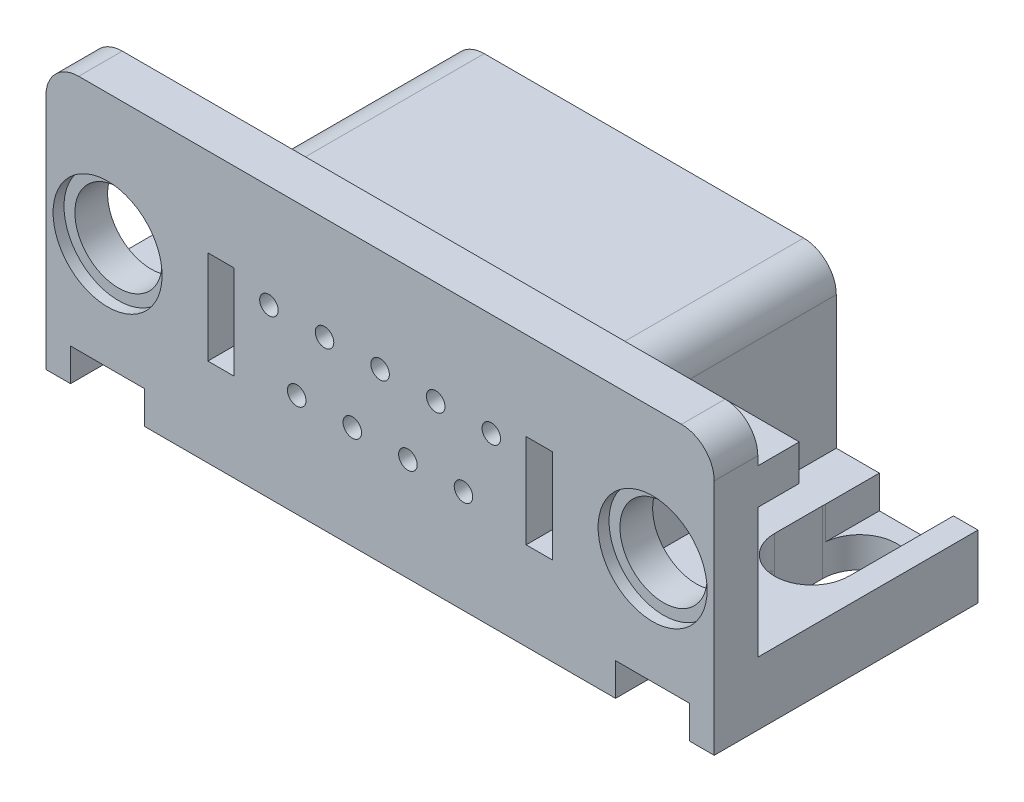
SolidWorks part; units mm, degrees
ref_plane "Front Plane" through (0, 0, 0) normal (0, 0, 1) x (1, 0, 0)
ref_plane "Top Plane" through (0, 0, 0) normal (0, 1, 0) x (1, 0, 0)
ref_plane "Right Plane" through (0, 0, 0) normal (1, 0, 0) x (0, 0, -1)
sketch "Sketch1" plane through (0, 0, 0) normal (0, 1, 0) x (1, 0, 0)
  line L1 (15.325, 6.05) -> (-15.325, 6.05)
  line L2 (15.325, 6.05) -> (15.325, -6.05)
  line L3 (15.325, -6.05) -> (-15.325, -6.05)
  line L4 (-15.325, 6.05) -> (-15.325, -6.05)
  line L5 (15.325, 6.05) -> (-15.325, -6.05) construction
  line L6 (15.325, -6.05) -> (-15.325, 6.05) construction
  point P0 (0, 0)
  dimension "D1" = 30.65
  dimension "D2" = 12.1
extrude "Boss-Extrude1" add sketch "Sketch1" along normal blind 12.4
sketch "Sketch2" plane through (0, 0, 6.05) normal (0, 0, 1) x (1, 0, 0)
  line L0 (-15.325, 12.4) -> (15.325, 12.4) construction
  line L2 (0, 0) -> (0, 12.4) construction
  line L4 (-6.7, 8.35) -> (-7.9, 8.35)
  line L5 (-6.7, 8.35) -> (-6.7, 4.05)
  line L6 (-6.7, 4.05) -> (-7.9, 4.05)
  line L7 (-7.9, 8.35) -> (-7.9, 4.05)
  line L8 (-6.7, 8.35) -> (-7.9, 4.05) construction
  line L9 (-6.7, 4.05) -> (-7.9, 8.35) construction
  line L14 (-15.325, 0) -> (15.325, 0) construction
  line L15 (6.7, 4.05) -> (7.9, 8.35) construction
  line L16 (6.7, 8.35) -> (7.9, 4.05) construction
  line L17 (7.9, 8.35) -> (7.9, 4.05)
  line L18 (6.7, 4.05) -> (7.9, 4.05)
  line L19 (6.7, 8.35) -> (6.7, 4.05)
  line L20 (6.7, 8.35) -> (7.9, 8.35)
  circle A0 centre (-12.5, 6.4) radius 2
  circle A1 centre (12.5, 6.4) radius 2
  point P10 (-7.3, 6.2)
  point P21 (7.3, 6.2)
  dimension "D1" = 4
  dimension "D2" = 14.5
  dimension "D3" = 6
  dimension "D4" = 4.3
  dimension "D5" = 6.7
  dimension "D6" = 1.2
  dimension "D7" = 4.05
extrude "Cut-Extrude1" cut sketch "Sketch2" against normal blind 10
sketch "Sketch3" plane through (0, 0, 6.05) normal (0, 0, 1) x (1, 0, 0)
  line L5 (-15.325, 12.4) -> (15.325, 12.4) construction
  line L6 (-15.325, 0) -> (15.325, 0) construction
  circle A0 centre (-5.1, 7.675) radius 0.425
  circle A2 centre (-2.55, 7.675) radius 0.425
  circle A3 centre (0, 7.675) radius 0.425
  circle A4 centre (2.55, 7.675) radius 0.425
  circle A5 centre (5.1, 7.675) radius 0.425
  circle A6 centre (-3.825, 4.725) radius 0.425
  circle A7 centre (-1.275, 4.725) radius 0.425
  circle A8 centre (1.275, 4.725) radius 0.425
  circle A9 centre (3.825, 4.725) radius 0.425
  dimension "D1" = 0.85
  dimension "D3" = 4.3
  dimension "D4" = 5
  dimension "D5" = 0.85
  dimension "D2" = 2.55
  dimension "D7" = 4.3
  dimension "D9" = 2.55
  dimension "D6" = 1.275
  dimension "D8" = 4
extrude "Cut-Extrude2" cut sketch "Sketch3" against normal blind 12.4
sketch "Sketch4" plane through (0, 0, -6.05) normal (0, 0, -1) x (-1, 0, 0)
  line L0 (15.325, 12.4) -> (15.325, 0) construction
  line L1 (-15.325, 12.4) -> (15.325, 12.4)
  line L2 (-15.325, 12.4) -> (-15.325, 10.5)
  line L3 (-15.325, 10.5) -> (15.325, 10.5)
  line L4 (15.325, 12.4) -> (15.325, 10.5)
  line L5 (-15.325, 0) -> (15.325, 0) construction
  line L6 (-8.8, 0) -> (8.8, 0)
  line L7 (-8.8, 0) -> (-8.8, 0.8)
  line L8 (-8.8, 0.8) -> (8.8, 0.8)
  line L9 (8.8, 0) -> (8.8, 0.8)
  line L10 (0, 0) -> (0, 10.5) construction
  line L11 (15.325, 8.85) -> (8.825, 8.85)
  line L12 (15.325, 8.85) -> (15.325, 2.9)
  line L13 (15.325, 2.9) -> (8.825, 2.9)
  line L14 (8.825, 8.85) -> (8.825, 2.9)
  line L15 (-15.325, 2.9) -> (-8.825, 2.9)
  line L16 (-8.825, 8.85) -> (-8.825, 2.9)
  line L17 (-15.325, 8.85) -> (-8.825, 8.85)
  line L18 (-15.325, 8.85) -> (-15.325, 2.9)
  point P13 (0, 0.8)
  dimension "D1" = 1.9
  dimension "D2" = 17.6
  dimension "D3" = 0.8
  dimension "D4" = 1.65
  dimension "D5" = 6.5
  dimension "D6" = 2.9
extrude "Cut-Extrude3" cut sketch "Sketch4" against normal blind 10.1
sketch "Sketch6" plane through (0, 10.5, 0) normal (0, 1, 0) x (1, 0, 0)
  line L0 (-15.325, -6.05) -> (15.325, -6.05) construction
  line L1 (15.325, 6.05) -> (8.825, 6.05)
  line L2 (15.325, 6.05) -> (15.325, -2.15)
  line L3 (15.325, -2.15) -> (8.825, -2.15)
  line L4 (8.825, 6.05) -> (8.825, -2.15)
  line L7 (0, 0) -> (0, -6.05) construction
  line L8 (-8.825, 6.05) -> (-8.825, -2.15)
  line L9 (-15.325, -2.15) -> (-8.825, -2.15)
  line L10 (-15.325, 6.05) -> (-15.325, -2.15)
  line L11 (-15.325, 6.05) -> (-8.825, 6.05)
  dimension "D1" = 3.9
  dimension "D2" = 6.5
extrude "Cut-Extrude4" cut sketch "Sketch6" against normal up to next
sketch "Sketch7" plane through (0, 0, -6.05) normal (0, 0, -1) x (-1, 0, 0)
  line L5 (-15.325, 9.5) -> (15.325, 9.5)
  line L6 (-7.825, 9.5) -> (7.825, 9.5)
  line L8 (-7.825, 2.9) -> (-7.825, 10.5)
  line L9 (-7.825, 2.9) -> (-7.825, 9.5)
  line L10 (-7.825, 2.9) -> (7.825, 2.9)
  line L11 (7.825, 10.5) -> (7.825, 2.9)
  line L12 (7.825, 9.5) -> (7.825, 2.9)
  dimension "D2" = 1
  dimension "D1" = 1
  dimension "D3" = 1
extrude "Cut-Extrude5" cut sketch "Sketch7" against normal blind 6.35
sketch "Sketch8" plane through (0, 2.9, 0) normal (0, 1, 0) x (1, 0, 0)
  line L0 (-12.495, 3.45) -> (-12.495, 1.25) construction
  line L1 (-10.795, 3.45) -> (-10.795, 1.25)
  line L2 (-14.195, 3.45) -> (-14.195, 1.25)
  line L3 (-8.825, 6.05) -> (-15.325, 6.05) construction
  line L6 (-15.325, -4.05) -> (-15.325, 6.05) construction
  line L7 (0, 0) -> (0, -6.05) construction
  line L8 (-15.325, -6.05) -> (15.325, -6.05) construction
  line L9 (12.495, 3.45) -> (12.495, 1.25) construction
  line L10 (10.795, 3.45) -> (10.795, 1.25)
  line L11 (14.195, 3.45) -> (14.195, 1.25)
  arc A0 (-10.795, 3.45) -> (-14.195, 3.45) centre (-12.495, 3.45) ccw
  arc A1 (-14.195, 1.25) -> (-10.795, 1.25) centre (-12.495, 1.25) ccw
  arc A2 (10.795, 3.45) -> (14.195, 3.45) centre (12.495, 3.45) cw
  arc A3 (14.195, 1.25) -> (10.795, 1.25) centre (12.495, 1.25) cw
  point P2 (-12.495, 2.35)
  point P18 (12.495, 2.35)
  dimension "D1" = 1.7
  dimension "D2" = 5.6
  dimension "D3" = 0.9
  dimension "D4" = 2.83
extrude "Cut-Extrude6" cut sketch "Sketch8" against normal up to next
fillet "Fillet1" radius 1.5 2 edges at (-8.825, 10.5, -1.95) (8.825, 10.5, -1.95)
sketch "Sketch10" plane through (0, 0, -6.05) normal (0, 0, -1) x (-1, 0, 0)
  line L0 (-15.325, 2.9) -> (-8.825, 2.9) construction
  line L1 (-10.8, 4.4) -> (-14.2, 4.4)
  line L2 (-10.8, 4.4) -> (-10.8, 1.4)
  line L3 (-10.8, 1.4) -> (-14.2, 1.4)
  line L4 (-14.2, 4.4) -> (-14.2, 1.4)
  line L5 (-10.8, 4.4) -> (-14.2, 1.4) construction
  line L6 (-10.8, 1.4) -> (-14.2, 4.4) construction
  point P0 (-12.5, 2.9)
  point P7 (-12.5, 6.4)
  dimension "D1" = 3.4
  dimension "D2" = 3
extrude "Cut-Extrude7" cut sketch "Sketch10" against normal up to vertex (4.8 mm away) up to point (10.795, 2.9, -1.25)
sketch "Sketch11" plane through (0, 0, 6.05) normal (0, 0, 1) x (1, 0, 0)
  line L0 (-15.325, 0) -> (15.325, 0) construction
  line L1 (14.2, 1.5) -> (10.8, 1.5)
  line L2 (14.2, 1.5) -> (14.2, -1.5)
  line L3 (14.2, -1.5) -> (10.8, -1.5)
  line L4 (10.8, 1.5) -> (10.8, -1.5)
  line L5 (14.2, 1.5) -> (10.8, -1.5) construction
  line L6 (14.2, -1.5) -> (10.8, 1.5) construction
  point P0 (12.5, 0)
  point P7 (12.5, 6.4)
  dimension "D1" = 3.4
  dimension "D2" = 3
extrude "Cut-Extrude8" cut sketch "Sketch11" against normal up to vertex (9.5 mm away) up to point (10.795, 0, -3.45)
mirror "Mirror3" about plane through (0, 0, 0) normal (1, 0, 0) of "Cut-Extrude8", "Cut-Extrude7"
fillet "Fillet2" radius 1.5 2 edges at (15.325, 12.4, 5.05) (-15.325, 12.4, 5.05)
sketch "Sketch12" plane through (0, 0, 6.05) normal (0, 0, 1) x (1, 0, 0)
  circle A2 centre (-12.5, 6.4) radius 2.5
  circle A3 centre (-12.5, 6.4) radius 2.5
  circle A5 centre (12.5, 6.4) radius 2.5
  circle A6 centre (12.5, 6.4) radius 2.5
  dimension "D1" = 0.5
  dimension "D2" = 0.5
extrude "Cut-Extrude9" cut sketch "Sketch12" against normal blind 0.5
sketch "Sketch13" plane through (0, 0.8, 0) normal (0, -1, 0) x (1, 0, 0)
  line L0 (-8.8, -6.05) -> (8.8, -6.05) construction
  line L1 (4.695, -6.05) -> (5.495, -6.05)
  line L2 (4.695, -6.05) -> (4.695, -4.45)
  line L3 (4.695, -4.45) -> (5.495, -4.45)
  line L4 (5.495, -6.05) -> (5.495, -4.45)
  line L7 (15.325, 6.05) -> (15.325, -6.05) construction
  line L9 (1.675, -6.05) -> (1.675, -1.55)
  line L10 (4.225, -6.05) -> (3.425, -6.05)
  line L11 (4.225, -6.05) -> (4.225, -1.55)
  line L12 (4.225, -1.55) -> (3.425, -1.55)
  line L13 (3.425, -6.05) -> (3.425, -1.55)
  line L14 (1.675, -6.05) -> (0.875, -6.05)
  line L15 (0.875, -6.05) -> (0.875, -1.55)
  line L16 (1.675, -1.55) -> (0.875, -1.55)
  line L17 (2.145, -6.05) -> (2.145, -4.45)
  line L18 (2.145, -6.05) -> (2.945, -6.05)
  line L19 (2.945, -6.05) -> (2.945, -4.45)
  line L20 (2.145, -4.45) -> (2.945, -4.45)
  line L21 (-0.875, -6.05) -> (-0.875, -1.55)
  line L22 (-0.875, -6.05) -> (-1.675, -6.05)
  line L23 (-1.675, -6.05) -> (-1.675, -1.55)
  line L24 (-0.875, -1.55) -> (-1.675, -1.55)
  line L25 (-0.405, -6.05) -> (-0.405, -4.45)
  line L26 (-0.405, -6.05) -> (0.395, -6.05)
  line L27 (0.395, -6.05) -> (0.395, -4.45)
  line L28 (-0.405, -4.45) -> (0.395, -4.45)
  line L29 (-3.425, -6.05) -> (-3.425, -1.55)
  line L30 (-3.425, -6.05) -> (-4.225, -6.05)
  line L31 (-4.225, -6.05) -> (-4.225, -1.55)
  line L32 (-3.425, -1.55) -> (-4.225, -1.55)
  line L33 (-2.955, -6.05) -> (-2.955, -4.45)
  line L34 (-2.955, -6.05) -> (-2.155, -6.05)
  line L35 (-2.155, -6.05) -> (-2.155, -4.45)
  line L36 (-2.955, -4.45) -> (-2.155, -4.45)
  line L37 (-15.325, -6.05) -> (-15.325, 6.05) construction
  line L38 (-4.695, -6.05) -> (-5.495, -6.05)
  line L39 (-4.695, -6.05) -> (-4.695, -4.45)
  line L40 (-4.695, -4.45) -> (-5.495, -4.45)
  line L41 (-5.495, -6.05) -> (-5.495, -4.45)
  point P8 (5.095, -4.45)
  point P11 (3.825, -1.55)
  point P44 (-5.095, -6.05)
  dimension "D1" = 1.6
  dimension "D2" = 10.23
  dimension "D3" = 0.8
  dimension "D4" = 0.8
  dimension "D5" = 11.5
  dimension "D6" = 4.5
  dimension "D8" = 0.8
  dimension "D9" = 10.23
  dimension "D10" = 2.55
  dimension "D11" = 1.6
  dimension "D7" = 4
extrude "Cut-Extrude10" cut sketch "Sketch13" against normal up to next
fillet "Fillet3" radius 0.25 18 edges at (-4.695, 1.85, -6.05) (-4.225, 1.85, -6.05) (-3.425, 1.85, -6.05) (-2.955, 1.85, -6.05) (-2.155, 1.85, -6.05) (-1.675, 1.85, -6.05) (-0.875, 1.85, -6.05) (-0.405, 1.85, -6.05) (0.395, 1.85, -6.05) (0.875, 1.85, -6.05) (1.675, 1.85, -6.05) (2.145, 1.85, -6.05) (2.945, 1.85, -6.05) (3.425, 1.85, -6.05) (4.225, 1.85, -6.05) (4.695, 1.85, -6.05) (5.495, 1.85, -6.05) (-5.495, 1.85, -6.05)
sketch "Sketch14" plane through (0, 0, 0.3) normal (0, 0, -1) x (-1, 0, 0)
  circle A9 centre (-2.55, 7.675) radius 0.725
  circle A10 centre (-5.1, 7.675) radius 0.725
  circle A11 centre (-5.1, 7.675) radius 0.725
  circle A12 centre (0, 7.675) radius 0.725
  circle A13 centre (2.55, 7.675) radius 0.725
  circle A14 centre (5.1, 7.675) radius 0.725
  circle A15 centre (3.825, 4.725) radius 0.725
  circle A16 centre (1.275, 4.725) radius 0.725
  circle A17 centre (-1.275, 4.725) radius 0.725
  circle A18 centre (-3.825, 4.725) radius 0.725
  dimension "D1" = 0.3
extrude "Cut-Extrude11" cut sketch "Sketch14" against normal blind 1
